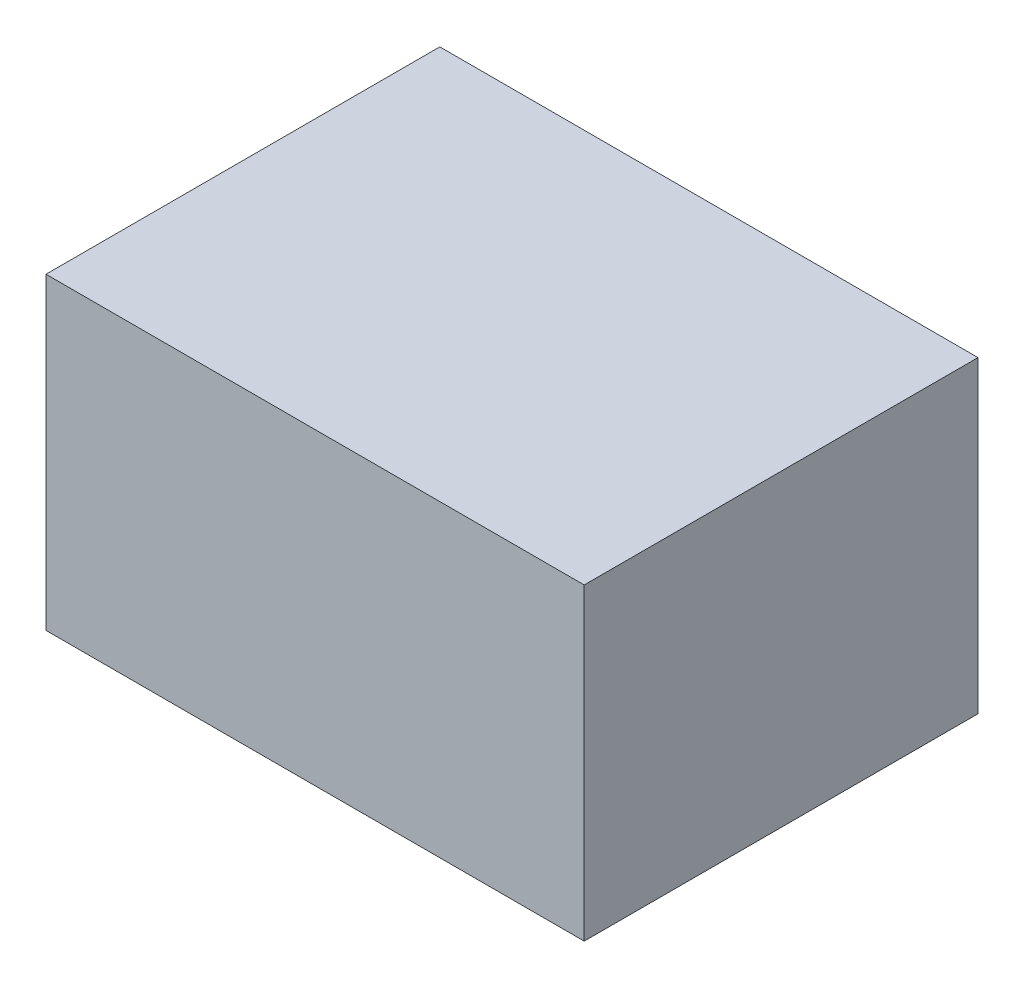
SolidWorks part; units mm, degrees
ref_plane "Front Plane" through (0, 0, 0) normal (0, 0, 1) x (1, 0, 0)
ref_plane "Top Plane" through (0, 0, 0) normal (0, 1, 0) x (1, 0, 0)
ref_plane "Right Plane" through (0, 0, 0) normal (1, 0, 0) x (0, 0, -1)
sketch "Sketch1" plane through (0, 0, 0) normal (0, 0, 1) x (1, 0, 0)
  line L1 (-52.07, -29.845) -> (52.07, -29.845)
  line L2 (-52.07, -29.845) -> (-52.07, 29.845)
  line L3 (-52.07, 29.845) -> (52.07, 29.845)
  line L4 (52.07, -29.845) -> (52.07, 29.845)
  line L5 (-52.07, -29.845) -> (52.07, 29.845) construction
  line L6 (-52.07, 29.845) -> (52.07, -29.845) construction
  point P0 (0, 0)
  dimension "D1" = 59.69
  dimension "D2" = 104.14
extrude "Extrude1" add sketch "Sketch1" along normal mid plane 76.2
sketch "Sketch3" plane through (52.07, 0, 0) normal (1, 0, 0) x (0, 0, -1)
  line L0 (38.1, -29.845) -> (38.1, 29.845) construction
  line L1 (-38.1, -29.845) -> (-38.1, 29.845) construction
  point P0 (38.1, 0)
  point P1 (-38.1, 0)
sketch "Sketch8" plane through (0, 0, -38.1) normal (0, 0, -1) x (-1, 0, 0)
  point P0 (0, 0)
